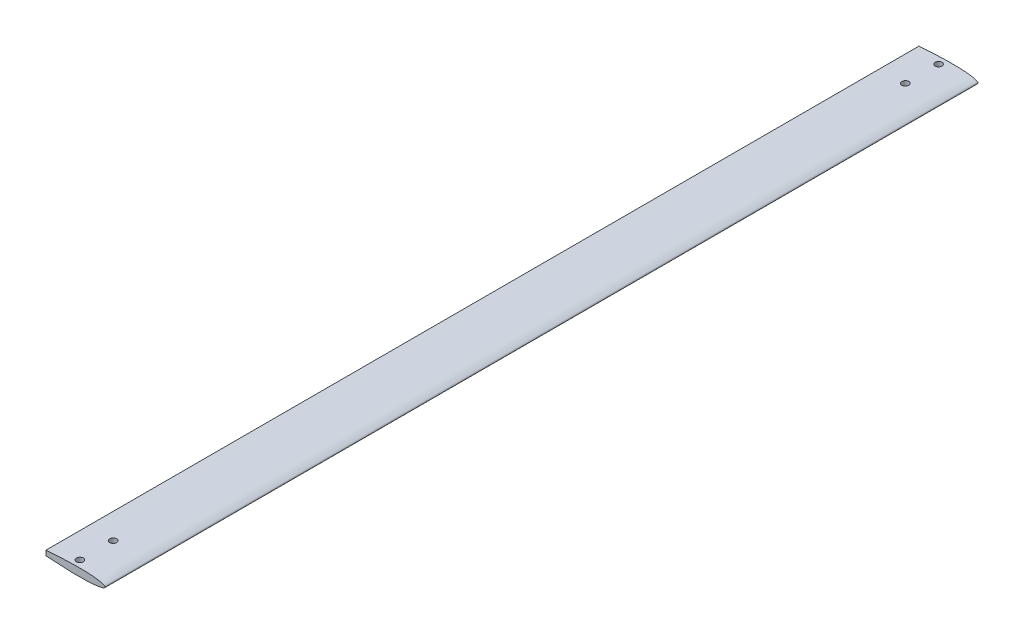
SolidWorks part; units mm, degrees
ref_plane "Front Plane" through (0, 0, 0) normal (0, 0, 1) x (1, 0, 0)
ref_plane "Top Plane" through (0, 0, 0) normal (0, 1, 0) x (1, 0, 0)
ref_plane "Right Plane" through (0, 0, 0) normal (1, 0, 0) x (0, 0, -1)
sketch "Sketch1" plane through (0, 0, 0) normal (0, 0, 1) x (1, 0, 0)
  line L0 (-62.0201, 2.6345) -> (-62.0201, -2.6345)
  spline S0 degree 3 poles (-62.0201, 2.6345) (-61.2451, 2.6899) (-58.9339, 2.8552) (-55.0506, 3.1054) (-50.3534, 3.3832) (-45.604, 3.628) (-40.8545, 3.8326) (-36.157, 3.9877) (-31.5628, 4.085) (-27.1223, 4.1172) (-22.884, 4.0788) (-18.8944, 3.9662) (-15.197, 3.7784) (-11.8322, 3.517) (-8.8366, 3.186) (-6.2419, 2.7923) (-4.0765, 2.3423) (-2.3561, 1.8514) (-1.0992, 1.3124) (-0.2619, 0.7555) (0.1083, 0) (-0.2619, -0.7555) (-1.0992, -1.3124) (-2.3561, -1.8514) (-4.0765, -2.3423) (-6.2419, -2.7923) (-8.8366, -3.186) (-11.8322, -3.517) (-15.197, -3.7784) (-18.8944, -3.9662) (-22.884, -4.0788) (-27.1223, -4.1172) (-31.5628, -4.085) (-36.157, -3.9877) (-40.8545, -3.8326) (-45.604, -3.628) (-50.3534, -3.3832) (-55.0506, -3.1054) (-58.9339, -2.8552) (-61.2451, -2.6899) (-62.0201, -2.6345) knots 0 0 0 0 0.018499 0.055171 0.092655 0.130539 0.168407 0.205846 0.242449 0.277819 0.311577 0.343364 0.372846 0.399719 0.423712 0.444594 0.46218 0.476354 0.487106 0.494669 0.5 0.505331 0.512894 0.523646 0.53782 0.555406 0.576288 0.600281 0.627154 0.656636 0.688423 0.722181 0.757551 0.794154 0.831593 0.869461 0.907345 0.944829 0.981501 1 1 1 1
extrude "Boss-Extrude1" add sketch "Sketch1" along normal mid plane 917.4
ref_plane "Plane1" through (0, -10, 0) normal (0, 1, 0) x (1, 0, 0)
sketch "Sketch2" plane through (0, -10, 0) normal (0, 1, 0) x (1, 0, 0)
  circle A0 centre (-33.9, -451.2) radius 3.6
  circle A1 centre (-33.9, -416.2) radius 3.6
  circle A2 centre (-33.9, 416.2) radius 3.6
  circle A3 centre (-33.9, 451.2) radius 3.6
extrude "Cut-Extrude1" cut sketch "Sketch2" along normal blind 20
